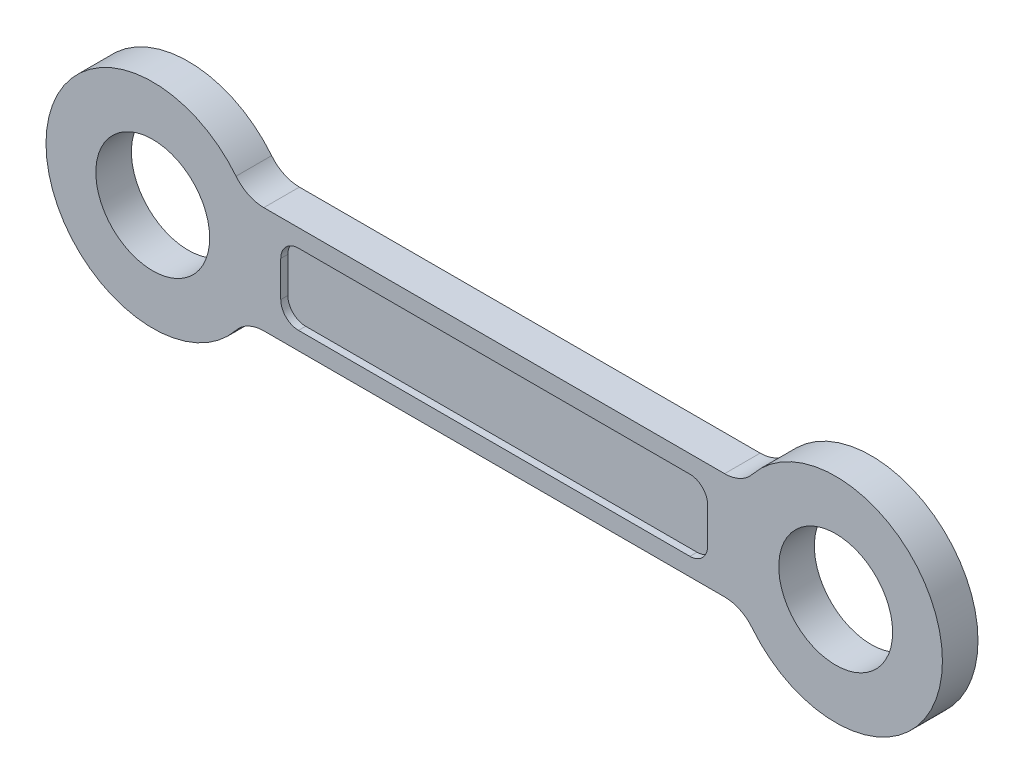
SolidWorks part; units mm, degrees
ref_plane "Front Plane" through (0, 0, 0) normal (0, 0, 1) x (1, 0, 0)
ref_plane "Top Plane" through (0, 0, 0) normal (0, 1, 0) x (1, 0, 0)
ref_plane "Right Plane" through (0, 0, 0) normal (1, 0, 0) x (0, 0, -1)
sketch "Sketch1" plane through (0, 0, 0) normal (0, 0, 1) x (1, 0, 0)
  line L1 (-70, -15) -> (70, -15)
  line L3 (-70, 15) -> (70, 15)
  line L5 (-70, -15) -> (70, 15) construction
  line L6 (-70, 15) -> (70, -15) construction
  arc A0 (70, -15) -> (70, 15) centre (95.9808, 0) ccw
  arc A1 (-70, 15) -> (-70, -15) centre (-95.9808, 0) ccw
  circle A2 centre (-95.9808, 0) radius 16
  circle A3 centre (95.9808, 0) radius 16
  point P0 (0, 0)
  point P7 (0, 0)
  point P9 (0, 0)
  dimension "D3" = 60
  dimension "D4" = 60
  dimension "D5" = 32
  dimension "D6" = 32
  dimension "D1" = 140
  dimension "D2" = 30
extrude "Boss-Extrude1" add sketch "Sketch1" along normal blind 5 and the other way blind 5
fillet "Fillet1" radius 10 4 edges at (70, -15, 0) (70, 15, 0) (-70, 15, 0) (-70, -15, 0)
sketch "Sketch2" plane through (0, 0, 5) normal (0, 0, 1) x (1, 0, 0)
  line L1 (55, 10) -> (-55, 10)
  line L2 (60, 5) -> (60, -5)
  line L3 (55, -10) -> (-55, -10)
  line L4 (-60, 5) -> (-60, -5)
  line L5 (60, 10) -> (-60, -10) construction
  line L6 (60, -10) -> (-60, 10) construction
  arc A0 (60, -5) -> (55, -10) centre (55, -5) cw
  arc A1 (55, 10) -> (60, 5) centre (55, 5) cw
  arc A2 (-55, -10) -> (-60, -5) centre (-55, -5) cw
  arc A3 (-55, 10) -> (-60, 5) centre (-55, 5) ccw
  point P0 (0, 0)
  dimension "D3" = 5
  dimension "D1" = 120
  dimension "D2" = 20
extrude "Cut-Extrude1" cut sketch "Sketch2" against normal blind 2
mirror "Mirror4" about plane through (0, 0, 0) normal (0, 0, 1) of "Cut-Extrude1"
